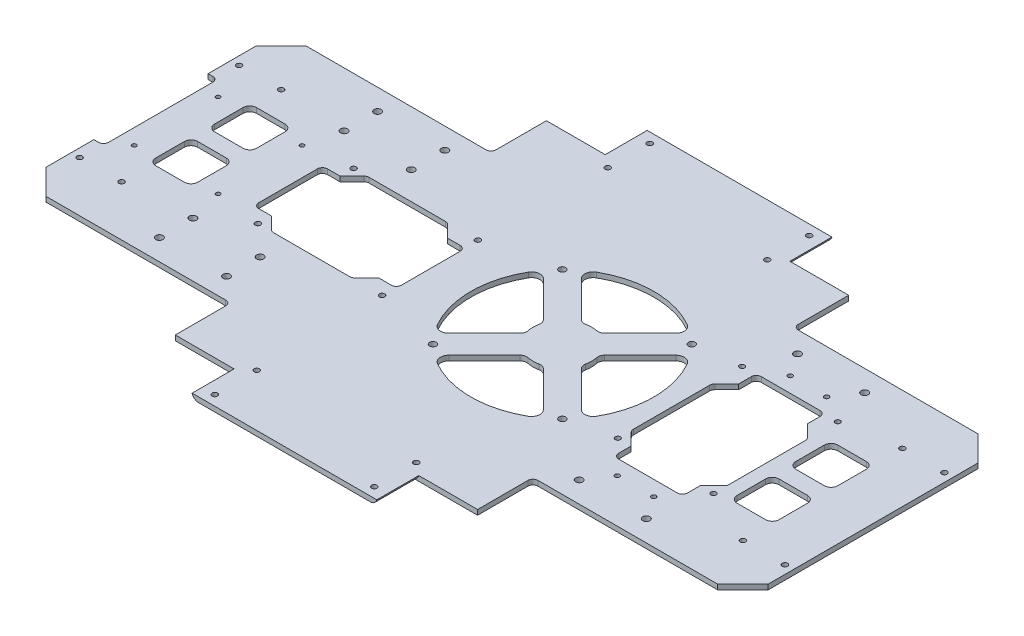
SolidWorks part; units mm, degrees
ref_plane "前视基准面" through (0, 0, 0) normal (0, 0, 1) x (1, 0, 0)
ref_plane "上视基准面" through (0, 0, 0) normal (0, 1, 0) x (1, 0, 0)
ref_plane "右视基准面" through (0, 0, 0) normal (1, 0, 0) x (0, 0, -1)
sketch "草图1" plane through (0, 0, 0) normal (0, 1, 0) x (1, 0, 0)
  line L0 (-82.9301, 135.4999) -> (-82.9301, 112.4999)
  line L1 (77.0699, 77.4999) -> (77.0699, -77.4999)
  line L2 (-47.9301, 77.4999) -> (77.0699, 77.4999)
  line L3 (-137.9301, 0) -> (-352.9301, 0) construction
  line L4 (-47.9301, -77.4999) -> (77.0699, -77.4999)
  line L5 (-137.9301, 112.4999) -> (-137.9301, -112.4999) construction
  line L6 (-137.9301, 0) -> (77.0699, 0) construction
  line L7 (-227.9301, -77.4999) -> (-352.9301, -77.4999)
  line L8 (-82.9301, 135.4999) -> (-192.9301, 135.4999)
  line L9 (-192.9301, 135.4999) -> (-192.9301, 112.4999)
  line L10 (-192.9301, -135.4999) -> (-82.9301, -135.4999)
  line L11 (-82.9301, -135.4999) -> (-82.9301, -112.4999)
  line L12 (-47.9301, 112.4999) -> (-47.9301, 77.4999)
  line L13 (-227.9301, 77.4999) -> (-352.9301, 77.4999)
  line L14 (-352.9301, 77.4999) -> (-352.9301, -77.4999)
  line L15 (-192.9301, -112.4999) -> (-192.9301, -135.4999)
  line L16 (-47.9301, -112.4999) -> (-82.9301, -112.4999)
  line L17 (-47.9301, 112.4999) -> (-82.9301, 112.4999)
  line L18 (-47.9301, -112.4999) -> (-47.9301, -77.4999)
  line L19 (-227.9301, -112.4999) -> (-227.9301, -77.4999)
  line L20 (-227.9301, -112.4999) -> (-192.9301, -112.4999)
  line L21 (-227.9301, 112.4999) -> (-192.9301, 112.4999)
  line L22 (-227.9301, 112.4999) -> (-227.9301, 77.4999)
  point P7 (77.0699, 0)
extrude "凸台-拉伸1" add sketch "草图1" along normal blind 3
fillet "圆角1" radius 3 8 edges at (-227.9301, 1.5, -77.4999) (-192.9301, 1.5, -112.4999) (-227.9301, 1.5, 77.4999) (-192.9301, 1.5, 112.4999) (-82.9301, 1.5, 112.4999) (-47.9301, 1.5, 77.4999) (-47.9301, 1.5, -77.4999) (-82.9301, 1.5, -112.4999)
sketch "草图2" plane through (0, 3, 0) normal (0, 1, 0) x (1, 0, 0)
  line L0 (77.0699, 47.5) -> (72.0699, 47.5) construction
  line L1 (72.0699, 47.5) -> (47.0699, 47.5) construction
  line L2 (47.0699, 47.5) -> (47.0699, -47.5) construction
  line L3 (47.0699, -47.5) -> (72.0699, -47.5) construction
  line L4 (72.0699, -47.5) -> (72.0699, 47.5) construction
  line L5 (72.0699, -47.5) -> (77.0699, -47.5) construction
  line L6 (77.0699, 0) -> (-352.9301, 0) construction
  line L7 (77.0699, -77.4999) -> (77.0699, 77.4999) construction
  line L8 (-352.9301, 77.4999) -> (-352.9301, -77.4999) construction
  line L9 (77.0699, 47.5) -> (77.0699, -47.5) construction
  line L10 (-137.9301, 135.4999) -> (-137.9301, -135.4999) construction
  line L11 (-82.9301, 135.4999) -> (-192.9301, 135.4999) construction
  line L12 (-192.9301, -135.4999) -> (-82.9301, -135.4999) construction
  line L13 (-90.4301, 104.4999) -> (-90.4301, 129.4999) construction
  line L14 (-90.4301, 129.4999) -> (-90.4301, 135.4999) construction
  line L15 (-185.4301, 135.4999) -> (-185.4301, 129.4999) construction
  line L16 (-185.4301, 104.4999) -> (-90.4301, 104.4999) construction
  line L17 (-185.4301, 135.4999) -> (-90.4301, 135.4999) construction
  line L18 (-185.4301, 129.4999) -> (-185.4301, 104.4999) construction
  line L19 (-90.4301, 129.4999) -> (-185.4301, 129.4999) construction
  line L20 (-90.4301, -129.4999) -> (-185.4301, -129.4999) construction
  line L21 (-185.4301, -129.4999) -> (-185.4301, -104.4999) construction
  line L22 (-185.4301, -135.4999) -> (-90.4301, -135.4999) construction
  line L23 (-185.4301, -104.4999) -> (-90.4301, -104.4999) construction
  line L24 (-185.4301, -135.4999) -> (-185.4301, -129.4999) construction
  line L25 (-90.4301, -129.4999) -> (-90.4301, -135.4999) construction
  line L26 (-90.4301, -104.4999) -> (-90.4301, -129.4999) construction
  line L27 (-352.9301, 47.5) -> (-352.9301, -47.5) construction
  line L28 (-347.9301, -47.5) -> (-352.9301, -47.5) construction
  line L29 (-347.9301, -47.5) -> (-347.9301, 47.5) construction
  line L30 (-322.9301, -47.5) -> (-347.9301, -47.5) construction
  line L31 (-322.9301, 47.5) -> (-322.9301, -47.5) construction
  line L32 (-347.9301, 47.5) -> (-322.9301, 47.5) construction
  line L33 (-352.9301, 47.5) -> (-347.9301, 47.5) construction
  circle A0 centre (47.0699, 47.5) radius 1.6
  circle A1 centre (72.0699, 47.5) radius 1.6
  circle A2 centre (47.0699, -47.5) radius 1.6
  circle A3 centre (72.0699, -47.5) radius 1.6
  circle A4 centre (-185.4301, 104.4999) radius 1.6
  circle A5 centre (-90.4301, 129.4999) radius 1.6
  circle A6 centre (-90.4301, 104.4999) radius 1.6
  circle A7 centre (-185.4301, 129.4999) radius 1.6
  circle A8 centre (-185.4301, -129.4999) radius 1.6
  circle A9 centre (-90.4301, -104.4999) radius 1.6
  circle A10 centre (-90.4301, -129.4999) radius 1.6
  circle A11 centre (-185.4301, -104.4999) radius 1.6
  circle A12 centre (-347.9301, -47.5) radius 1.6
  circle A13 centre (-322.9301, -47.5) radius 1.6
  circle A14 centre (-347.9301, 47.5) radius 1.6
  circle A15 centre (-322.9301, 47.5) radius 1.6
extrude "切除-拉伸1" cut sketch "草图2" against normal blind 47
sketch "草图3" plane through (0, 3, 0) normal (0, 1, 0) x (1, 0, 0)
  line L0 (-137.9301, 135.4999) -> (-137.9301, -135.4999) construction
  line L1 (-82.9301, 135.4999) -> (-192.9301, 135.4999) construction
  line L2 (-192.9301, -135.4999) -> (-82.9301, -135.4999) construction
  line L3 (-137.9301, 0) -> (-262.9301, 0) construction
  line L4 (-137.9301, 0) -> (-12.9301, 0) construction
  line L5 (-262.9301, 0) -> (-262.9301, 55) construction
  line L6 (-12.9301, -34) -> (-12.9301, 34) construction
  line L7 (-12.9301, 0) -> (-12.9301, 62) construction
  line L8 (-12.9301, 0) -> (-12.9301, -62) construction
  line L9 (-282.9301, -45) -> (-242.9301, -65) construction
  line L10 (-282.9301, 65) -> (-242.9301, 65) construction
  line L11 (-282.9301, 65) -> (-282.9301, 45) construction
  line L12 (-282.9301, 45) -> (-242.9301, 45) construction
  line L13 (-242.9301, 65) -> (-242.9301, 45) construction
  line L14 (-282.9301, 65) -> (-242.9301, 45) construction
  line L15 (-282.9301, 45) -> (-242.9301, 65) construction
  line L16 (-282.9301, -65) -> (-242.9301, -45) construction
  line L17 (-242.9301, -65) -> (-242.9301, -45) construction
  line L18 (-282.9301, -45) -> (-242.9301, -45) construction
  line L19 (-282.9301, -65) -> (-282.9301, -45) construction
  line L20 (-282.9301, -65) -> (-242.9301, -65) construction
  line L21 (7.0699, -65) -> (-32.9301, -65) construction
  line L22 (7.0699, -65) -> (7.0699, -45) construction
  line L23 (7.0699, -45) -> (-32.9301, -45) construction
  line L24 (-32.9301, -65) -> (-32.9301, -45) construction
  line L25 (7.0699, -65) -> (-32.9301, -45) construction
  line L26 (7.0699, 45) -> (-32.9301, 65) construction
  line L27 (7.0699, 65) -> (-32.9301, 45) construction
  line L28 (-32.9301, 65) -> (-32.9301, 45) construction
  line L29 (7.0699, 45) -> (-32.9301, 45) construction
  line L30 (7.0699, 65) -> (7.0699, 45) construction
  line L31 (7.0699, 65) -> (-32.9301, 65) construction
  line L32 (7.0699, -45) -> (-32.9301, -65) construction
  line L33 (-12.9301, 0) -> (-12.9301, -62) construction
  line L34 (-12.9301, 0) -> (-12.9301, 55) construction
  line L35 (-337.9301, 25) -> (-337.9301, -25) construction
  line L36 (-23.767, 51.5) -> (-12.9301, 34) construction
  line L37 (-352.9301, 77.4999) -> (-352.9301, -77.4999) construction
  line L38 (-23.767, 51.5) -> (-2.0931, 51.5) construction
  line L39 (-12.9301, 34) -> (-2.0931, 51.5) construction
  line L40 (-12.9301, -34) -> (-23.767, -51.5) construction
  line L41 (-23.767, -51.5) -> (-2.0931, -51.5) construction
  line L42 (-2.0931, -51.5) -> (-12.9301, -34) construction
  line L43 (-30.1258, 30) -> (4.2656, 30) construction
  line L44 (-30.1258, 35) -> (4.2656, 35)
  line L45 (-30.1258, 25) -> (-12.9301, 25)
  line L46 (-30.1258, 12.5) -> (4.2656, 12.5) construction
  line L47 (-30.1258, 17.5) -> (4.2656, 17.5)
  line L48 (-30.1258, 7.5) -> (4.2656, 7.5)
  line L49 (-30.1258, -30) -> (4.2656, -30) construction
  line L50 (-30.1258, -35) -> (4.2656, -35)
  line L51 (-30.1258, -25) -> (4.2656, -25)
  line L52 (-30.1258, -12.5) -> (4.2656, -12.5) construction
  line L53 (-30.1258, -17.5) -> (4.2656, -17.5)
  line L54 (-30.1258, -7.5) -> (4.2656, -7.5)
  line L55 (-8.9301, 25) -> (4.2656, 25)
  line L57 (-12.9301, 25) -> (-8.9301, 25)
  line L60 (-16.9301, -35) -> (-8.9301, 35) construction
  line L61 (-16.9301, 35) -> (-8.9301, -35) construction
  circle A0 centre (-282.9301, 65) radius 2.1
  circle A1 centre (-282.9301, 45) radius 2.1
  circle A2 centre (-242.9301, 65) radius 2.1
  circle A3 centre (-242.9301, 45) radius 2.1
  circle A4 centre (-242.9301, -45) radius 2.1
  circle A5 centre (-242.9301, -65) radius 2.1
  circle A6 centre (-282.9301, -45) radius 2.1
  circle A7 centre (-282.9301, -65) radius 2.1
  circle A8 centre (7.0699, -65) radius 2.1
  circle A9 centre (7.0699, -45) radius 2.1
  circle A10 centre (-32.9301, -65) radius 2.1
  circle A11 centre (-32.9301, -45) radius 2.1
  circle A12 centre (-32.9301, 45) radius 2.1
  circle A13 centre (-32.9301, 65) radius 2.1
  circle A14 centre (7.0699, 45) radius 2.1
  circle A15 centre (7.0699, 65) radius 2.1
  circle A16 centre (-23.767, -51.5) radius 1.4
  circle A17 centre (-2.0931, -51.5) radius 1.4
  arc A18 (-30.1258, 35) -> (-30.1258, 25) centre (-30.1258, 30) ccw
  circle A19 centre (-23.767, 51.5) radius 1.4
  arc A20 (4.2656, 25) -> (4.2656, 35) centre (4.2656, 30) ccw
  circle A21 centre (-2.0931, 51.5) radius 1.4
  circle A22 centre (-337.9301, 25) radius 1.25
  circle A23 centre (-287.9301, 25) radius 1.25
  circle A24 centre (-287.9301, -25) radius 1.25
  circle A25 centre (-337.9301, -25) radius 1.25
  arc A26 (-30.1258, 17.5) -> (-30.1258, 7.5) centre (-30.1258, 12.5) ccw
  arc A27 (4.2656, 7.5) -> (4.2656, 17.5) centre (4.2656, 12.5) ccw
  arc A28 (-30.1258, -35) -> (-30.1258, -25) centre (-30.1258, -30) cw
  arc A29 (4.2656, -25) -> (4.2656, -35) centre (4.2656, -30) cw
  arc A30 (-30.1258, -17.5) -> (-30.1258, -7.5) centre (-30.1258, -12.5) cw
  arc A31 (4.2656, -7.5) -> (4.2656, -17.5) centre (4.2656, -12.5) cw
  point P66 (-352.9301, 0)
  point P68 (-12.9301, 30)
  point P76 (-12.9301, 12.5)
  point P83 (-12.9301, -30)
  point P90 (-12.9301, -12.5)
  dimension "D9" = 15
  dimension "D11" = 5
  dimension "D1" = 125
  dimension "D2" = 50
  dimension "D3" = 55
  dimension "D4" = 50
  dimension "D5" = 50
  dimension "D6" = 50
  dimension "D7" = 40
  dimension "D8" = 20
  dimension "D10" = 0
  dimension "D12" = 30
  dimension "D13" = 7.5
  dimension "D14" = 34.3914
extrude "切除-拉伸2" cut sketch "草图3" against normal blind 47
chamfer "倒角1" distance 15 angle 45 4 edges at (77.0699, 1.5, -77.4999) (77.0699, 1.5, 77.4999) (-352.9301, 1.5, 77.4999) (-352.9301, 1.5, -77.4999)
sketch "草图5" plane through (0, 3, 0) normal (0, 1, 0) x (1, 0, 0)
  line L0 (-68.5001, 28.1163) -> (-89.6587, 6.9576)
  line L1 (-89.6587, -6.9576) -> (-68.5001, -28.1163)
  line L2 (-79.8138, -39.43) -> (-100.9725, -18.2713)
  line L3 (-114.8877, -18.2713) -> (-136.0464, -39.43)
  line L4 (-147.3601, -28.1163) -> (-126.2014, -6.9576)
  line L5 (-126.2014, 6.9576) -> (-147.3601, 28.1163)
  line L6 (-136.0464, 39.43) -> (-114.8877, 18.2713)
  line L7 (-100.9725, 18.2713) -> (-79.8138, 39.43)
  line L8 (-102.3298, -7.7031) -> (-102.3298, 7.7679)
  line L9 (-104.3298, -2.9676) -> (-104.3298, -7.7031)
  line L10 (-104.3298, 7.7679) -> (-104.3298, 3.0324)
  line L11 (-116.9301, -0.9676) -> (-106.3298, -0.9676)
  line L12 (-106.3298, 1.0324) -> (-116.9301, 1.0324)
  line L13 (-352.9301, 0) -> (77.0699, 0) construction
  line L14 (-352.9301, 62.4999) -> (-352.9301, -62.4999) construction
  line L15 (77.0699, -62.4999) -> (77.0699, 62.4999) construction
  line L16 (-137.9301, -135.4999) -> (-137.9301, -67.6391) construction
  line L17 (-192.9301, -135.4999) -> (-82.9301, -135.4999) construction
  line L18 (-137.9301, -67.6391) -> (-107.9301, -67.6391) construction
  line L19 (-107.9301, -67.6391) -> (-107.9301, 0) construction
  circle A0 centre (-69.3928, 38.5373) radius 1.55
  circle A1 centre (-69.3928, -38.5373) radius 1.55
  circle A2 centre (-146.4674, -38.5373) radius 1.55
  circle A3 centre (-146.4674, 38.5373) radius 1.55
  arc A4 (-60.6246, -27.0637) -> (-60.6246, 27.0637) centre (-107.9301, 0) ccw
  arc A5 (-60.6246, 27.0637) -> (-68.5001, 28.1163) centre (-64.9645, 24.5808) ccw
  arc A6 (-89.6587, 6.9576) -> (-90.7559, 3.361) centre (-86.8303, 4.1292) ccw
  arc A7 (-90.7559, -3.361) -> (-90.7559, 3.361) centre (-107.9301, 0) ccw
  arc A8 (-90.7559, -3.361) -> (-89.6587, -6.9576) centre (-86.8303, -4.1292) ccw
  arc A9 (-68.5001, -28.1163) -> (-60.6246, -27.0637) centre (-64.9645, -24.5808) ccw
  arc A10 (-80.8664, -47.3055) -> (-79.8138, -39.43) centre (-83.3493, -42.9655) ccw
  arc A11 (-134.9937, -47.3055) -> (-80.8664, -47.3055) centre (-107.9301, 0) ccw
  arc A12 (-100.9725, -18.2713) -> (-104.5691, -17.1742) centre (-103.8009, -21.0998) ccw
  arc A13 (-111.291, -17.1742) -> (-104.5691, -17.1742) centre (-107.9301, 0) ccw
  arc A14 (-111.291, -17.1742) -> (-114.8877, -18.2713) centre (-112.0593, -21.0998) ccw
  arc A15 (-136.0464, -39.43) -> (-134.9937, -47.3055) centre (-132.5108, -42.9655) ccw
  arc A16 (-126.2014, -6.9576) -> (-125.1043, -3.361) centre (-129.0298, -4.1292) ccw
  arc A17 (-125.1043, 3.361) -> (-125.1043, -3.361) centre (-107.9301, 0) ccw
  arc A18 (-125.1043, 3.361) -> (-126.2014, 6.9576) centre (-129.0298, 4.1292) ccw
  arc A19 (-147.3601, 28.1163) -> (-155.2356, 27.0637) centre (-150.8956, 24.5808) ccw
  arc A20 (-155.2356, 27.0637) -> (-155.2356, -27.0637) centre (-107.9301, 0) ccw
  arc A21 (-155.2356, -27.0637) -> (-147.3601, -28.1163) centre (-150.8956, -24.5808) ccw
  arc A22 (-104.5691, 17.1742) -> (-111.291, 17.1742) centre (-107.9301, 0) ccw
  arc A23 (-114.8877, 18.2713) -> (-111.291, 17.1742) centre (-112.0593, 21.0998) ccw
  arc A24 (-104.5691, 17.1742) -> (-100.9725, 18.2713) centre (-103.8009, 21.0998) ccw
  arc A25 (-79.8138, 39.43) -> (-80.8664, 47.3055) centre (-83.3493, 42.9655) ccw
  arc A26 (-80.8664, 47.3055) -> (-134.9937, 47.3055) centre (-107.9301, 0) ccw
  arc A27 (-134.9937, 47.3055) -> (-136.0464, 39.43) centre (-132.5108, 42.9655) ccw
  arc A28 (-102.3298, 7.7679) -> (-104.3298, 7.7679) centre (-103.3298, 7.7679) ccw
  arc A29 (-104.3298, -7.7031) -> (-102.3298, -7.7031) centre (-103.3298, -7.7031) ccw
  arc A30 (-106.3298, 1.0324) -> (-104.3298, 3.0324) centre (-106.3298, 3.0324) ccw
  arc A31 (-104.3298, -2.9676) -> (-106.3298, -0.9676) centre (-106.3298, -2.9676) ccw
  arc A32 (-116.9301, 1.0324) -> (-116.9301, -0.9676) centre (-116.9301, 0.0324) ccw
extrude "切除-拉伸3" cut sketch "草图5" against normal blind 47
sketch "草图6" plane through (0, 3, 0) normal (0, 1, 0) x (1, 0, 0)
  line L0 (-260.7825, 28.5) -> (-186.7825, 28.5) construction
  line L1 (-260.7825, 28.5) -> (-260.7825, -28.5) construction
  line L2 (-260.7825, -28.5) -> (-186.7825, -28.5) construction
  line L3 (-186.7825, 28.5) -> (-186.7825, -28.5) construction
  line L4 (-352.9301, 0) -> (77.0699, 0) construction
  line L5 (-352.9301, 62.4999) -> (-352.9301, -62.4999) construction
  line L6 (77.0699, -62.4999) -> (77.0699, 62.4999) construction
  line L7 (-270.2825, -20.5) -> (-260.7825, -20.5)
  line L8 (-186.2825, -19.5) -> (-186.2825, 19.5)
  line L9 (-187.2825, 20.5) -> (-196.7825, 20.5)
  line L10 (-271.2825, 19.5) -> (-271.2825, -19.5)
  line L11 (-251.2825, -28.5) -> (-251.2825, -24.9) construction
  line L12 (-251.2825, -24.9) -> (-213.2825, -24.9) construction
  line L13 (-213.2825, -24.9) -> (-213.2825, -23.5) construction
  line L14 (-213.2825, -23.5) -> (-193.2825, -23.5) construction
  line L15 (-190.2825, -26.5) -> (-190.2825, -28.5) construction
  line L16 (-183.2825, -28.5) -> (-183.2825, 28.5) construction
  line L17 (-190.2825, 28.5) -> (-190.2825, 26.5) construction
  line L18 (-193.2825, 23.5) -> (-213.2825, 23.5) construction
  line L19 (-213.2825, 23.5) -> (-213.2825, 24.9) construction
  line L20 (-213.2825, 24.9) -> (-251.2825, 24.9) construction
  line L21 (-251.2825, 24.9) -> (-251.2825, 28.5) construction
  line L22 (-251.2825, 28.5) -> (-253.9086, 28.5) construction
  line L23 (-264.2825, 28.5) -> (-264.2825, 27.5) construction
  line L24 (-268.2825, 23.5) -> (-274.2825, 23.5) construction
  line L25 (-274.2825, 23.5) -> (-274.2825, -23.5) construction
  line L26 (-274.2825, -23.5) -> (-268.2825, -23.5) construction
  line L27 (-264.2825, -27.5) -> (-264.2825, -28.5) construction
  line L28 (-253.9086, -28.5) -> (-251.2825, -28.5) construction
  line L29 (-270.2825, 20.5) -> (-271.2825, 20.5)
  line L30 (-271.2825, 20.5) -> (-271.2825, 19.5)
  line L31 (-271.2825, -19.5) -> (-271.2825, -20.5)
  line L32 (-271.2825, -20.5) -> (-270.2825, -20.5)
  line L33 (-187.2825, -20.5) -> (-186.2825, -20.5)
  line L34 (-186.2825, -20.5) -> (-186.2825, -19.5)
  line L35 (-187.2825, 20.5) -> (-186.2825, 20.5)
  line L36 (-186.2825, 20.5) -> (-186.2825, 19.5)
  line L37 (-162.4301, 0) -> (-183.2825, 0) construction
  line L38 (-183.2825, 0) -> (-183.2825, 23.5) construction
  line L39 (-228.7825, 20.5) -> (-228.7825, 28.5) construction
  line L40 (-252.7825, 28.5) -> (-204.7825, 28.5)
  line L41 (-204.7825, 28.5) -> (-196.7825, 20.5)
  line L42 (-252.7825, 28.5) -> (-260.7825, 20.5)
  line L43 (-260.7825, 20.5) -> (-270.2825, 20.5)
  line L44 (-252.7825, -28.5) -> (-260.7825, -20.5)
  line L45 (-252.7825, -28.5) -> (-204.7825, -28.5)
  line L46 (-204.7825, -28.5) -> (-196.7825, -20.5)
  line L47 (-196.7825, -20.5) -> (-187.2825, -20.5)
  circle A0 centre (-260.7825, 28.5) radius 1.6
  circle A1 centre (-186.7825, 28.5) radius 1.6
  circle A2 centre (-260.7825, -28.5) radius 1.6
  circle A3 centre (-186.7825, -28.5) radius 1.6
  circle A4 centre (-186.7825, -28.5) radius 1.5 construction
  arc A5 (-190.2825, -26.5) -> (-193.2825, -23.5) centre (-193.2825, -26.5) ccw construction
  arc A6 (-190.2825, -28.5) -> (-183.2825, -28.5) centre (-186.7825, -28.5) ccw construction
  arc A7 (-183.2825, 28.5) -> (-190.2825, 28.5) centre (-186.7825, 28.5) ccw construction
  arc A8 (-193.2825, 23.5) -> (-190.2825, 26.5) centre (-193.2825, 26.5) ccw construction
  arc A9 (-257.9521, 30.5588) -> (-253.9086, 28.5) centre (-253.9086, 33.5) ccw construction
  arc A10 (-257.9521, 30.5588) -> (-264.2825, 28.5) centre (-260.7825, 28.5) ccw construction
  arc A11 (-268.2825, 23.5) -> (-264.2825, 27.5) centre (-268.2825, 27.5) ccw construction
  arc A12 (-264.2825, -27.5) -> (-268.2825, -23.5) centre (-268.2825, -27.5) ccw construction
  arc A13 (-264.2825, -28.5) -> (-257.9521, -30.5588) centre (-260.7825, -28.5) ccw construction
  arc A14 (-253.9086, -28.5) -> (-257.9521, -30.5588) centre (-253.9086, -33.5) ccw construction
  arc A15 (-155.2356, 27.0637) -> (-155.2356, -27.0637) centre (-107.9301, 0) ccw construction
  dimension "D1" = 3.2
  dimension "D2" = 3.2
  dimension "D3" = 3.2
  dimension "D4" = 3.2
extrude "切除-拉伸4" cut sketch "草图6" against normal blind 47
fillet "圆角2" radius 3 8 edges at (-204.7825, 1.5, 28.5) (-252.7825, 1.5, 28.5) (-271.2825, 1.5, 20.5) (-186.2825, 1.5, 20.5) (-186.2825, 1.5, -20.5) (-271.2825, 1.5, -20.5) (-204.7825, 1.5, -28.5) (-252.7825, 1.5, -28.5)
sketch "草图7" plane through (0, 3, 0) normal (0, 1, 0) x (1, 0, 0)
  line L1 (-337.9301, 25) -> (-337.9301, -25) construction
  line L2 (-337.9301, 0) -> (-347.1301, 0) construction
  line L3 (-347.1301, 0) -> (-347.1301, 34)
  line L4 (-347.1301, 0) -> (-347.1301, -34)
  line L5 (-347.1301, -34) -> (-352.9301, -34)
  line L6 (-352.9301, 62.4999) -> (-352.9301, -62.4999) construction
  line L7 (-347.1301, 34) -> (-352.9301, 34)
  line L8 (-352.9301, 34) -> (-352.9301, -34)
extrude "切除-拉伸5" cut sketch "草图7" against normal blind 47
fillet "圆角3" radius 3 2 edges at (-347.1301, 1.5, 34) (-347.1301, 1.5, -34)
sketch "草图8" plane through (0, 3, 0) normal (0, 1, 0) x (1, 0, 0)
  line L0 (-347.1301, 0) -> (-312.1301, 0)
  line L1 (77.0699, 0) -> (32.0699, 0) construction
  line L2 (-347.1301, -31) -> (-347.1301, 31) construction
  line L3 (-335.3508, 26.6608) -> (-288.9094, -26.6608) construction
  line L4 (-300.0305, -8.0391) -> (-300.0305, -25.0391)
  line L5 (-325.0305, -8.0391) -> (-325.0305, -25.0391)
  line L6 (-325.0305, 30.9609) -> (-300.0305, -29.0391) construction
  line L7 (-300.0305, 9.9609) -> (-300.0305, 26.9609)
  line L8 (77.0699, -62.4999) -> (77.0699, 62.4999) construction
  line L11 (47.0699, 9) -> (47.0699, 26)
  line L12 (26.0699, 5) -> (43.0699, 5)
  line L14 (26.0699, 30) -> (43.0699, 30)
  line L15 (22.0699, 9) -> (22.0699, 26)
  line L16 (22.0699, -9) -> (22.0699, -26)
  line L17 (26.0699, -30) -> (43.0699, -30)
  line L18 (26.0699, -5) -> (43.0699, -5)
  line L19 (47.0699, -9) -> (47.0699, -26)
  line L20 (-321.0305, 30.9609) -> (-304.0305, 30.9609)
  line L21 (-321.0305, 5.9609) -> (-304.0305, 5.9609)
  line L22 (-324.3388, -31.2402) -> (-300.0305, 30.9609) construction
  line L23 (-325.0305, 9.9609) -> (-325.0305, 26.9609)
  line L24 (-321.0305, -4.0391) -> (-304.0305, -4.0391)
  line L25 (-321.0305, -29.0391) -> (-304.0305, -29.0391)
  arc A0 (22.0699, -26) -> (26.0699, -30) centre (26.0699, -26) ccw
  arc A1 (43.0699, -30) -> (47.0699, -26) centre (43.0699, -26) ccw
  arc A2 (47.0699, -9) -> (43.0699, -5) centre (43.0699, -9) ccw
  arc A3 (26.0699, -5) -> (22.0699, -9) centre (26.0699, -9) ccw
  arc A4 (26.0699, 5) -> (22.0699, 9) centre (26.0699, 9) cw
  arc A5 (43.0699, 5) -> (47.0699, 9) centre (43.0699, 9) ccw
  arc A6 (47.0699, 26) -> (43.0699, 30) centre (43.0699, 26) ccw
  arc A7 (22.0699, 26) -> (26.0699, 30) centre (26.0699, 26) cw
  arc A8 (-300.0305, 26.9609) -> (-304.0305, 30.9609) centre (-304.0305, 26.9609) ccw
  arc A9 (-321.0305, -4.0391) -> (-325.0305, -8.0391) centre (-321.0305, -8.0391) ccw
  arc A10 (-325.0305, -25.0391) -> (-321.0305, -29.0391) centre (-321.0305, -25.0391) ccw
  arc A11 (-325.0305, 26.9609) -> (-321.0305, 30.9609) centre (-321.0305, 26.9609) cw
  arc A12 (-321.0305, 5.9609) -> (-325.0305, 9.9609) centre (-321.0305, 9.9609) cw
  arc A13 (-304.0305, -29.0391) -> (-300.0305, -25.0391) centre (-304.0305, -25.0391) ccw
  arc A14 (-304.0305, 5.9609) -> (-300.0305, 9.9609) centre (-304.0305, 9.9609) ccw
  arc A15 (-300.0305, -8.0391) -> (-304.0305, -4.0391) centre (-304.0305, -8.0391) ccw
  point P8 (-312.1301, 0)
  point P16 (34.9703, -0.9609)
  point P28 (22.0699, -30)
  point P34 (47.0699, -5)
  point P37 (22.0699, -5)
  point P40 (22.0699, 5)
  point P43 (47.0699, 5)
  dimension "D3" = 4
  dimension "D2" = 4
  dimension "D1" = 25
extrude "切除-拉伸6" cut sketch "草图8" against normal blind 47 contours L21 A14 L7 A8 L20 A11 L23 A12 | L4 A15 L24 A9 L5 A10 L25 A13 | A7 L15 A4 L12 A5 L11 A6 L14 | L18 A3 L16 A0 L17 A1 L19 A2
sketch "草图9" plane through (0, 3, 0) normal (0, 1, 0) x (1, 0, 0)
  line L0 (-137.9301, 135.4999) -> (-137.9301, 0) construction
  line L1 (-227.9301, 112.4999) -> (-198.5667, 112.4999)
  line L2 (-227.9301, 112.4999) -> (-227.9301, 110.4999)
  line L3 (-227.9301, 110.4999) -> (-192.9301, 110.4999)
  line L4 (-192.9301, 112.4999) -> (-192.9301, 110.4999)
  line L5 (-82.9301, 135.4999) -> (-192.9301, 135.4999) construction
  line L6 (-137.9301, 0) -> (77.0699, 0) construction
  line L7 (77.0699, -62.4999) -> (77.0699, 62.4999) construction
  line L8 (-192.9301, 112.4999) -> (-192.9301, 116.7715)
  line L9 (-192.9301, 116.7715) -> (-197.0435, 116.7715)
  line L10 (-197.0435, 116.7715) -> (-198.5667, 112.4999)
  line L11 (-78.8166, 116.7715) -> (-77.2934, 112.4999)
  line L12 (-82.9301, 116.7715) -> (-78.8166, 116.7715)
  line L13 (-82.9301, 112.4999) -> (-82.9301, 116.7715)
  line L14 (-82.9301, 112.4999) -> (-82.9301, 110.4999)
  line L15 (-47.9301, 110.4999) -> (-82.9301, 110.4999)
  line L16 (-47.9301, 112.4999) -> (-47.9301, 110.4999)
  line L17 (-47.9301, 112.4999) -> (-77.2934, 112.4999)
  line L18 (-47.9301, -112.4999) -> (-77.2934, -112.4999)
  line L19 (-47.9301, -112.4999) -> (-47.9301, -110.4999)
  line L20 (-47.9301, -110.4999) -> (-82.9301, -110.4999)
  line L21 (-82.9301, -112.4999) -> (-82.9301, -110.4999)
  line L22 (-82.9301, -112.4999) -> (-82.9301, -116.7715)
  line L23 (-82.9301, -116.7715) -> (-78.8166, -116.7715)
  line L24 (-78.8166, -116.7715) -> (-77.2934, -112.4999)
  line L25 (-197.0435, -116.7715) -> (-198.5667, -112.4999)
  line L26 (-192.9301, -116.7715) -> (-197.0435, -116.7715)
  line L27 (-192.9301, -112.4999) -> (-192.9301, -116.7715)
  line L28 (-192.9301, -112.4999) -> (-192.9301, -110.4999)
  line L29 (-227.9301, -110.4999) -> (-192.9301, -110.4999)
  line L30 (-227.9301, -112.4999) -> (-227.9301, -110.4999)
  line L31 (-227.9301, -112.4999) -> (-198.5667, -112.4999)
  dimension "D1" = 2
extrude "切除-拉伸7" cut sketch "草图9" against normal blind 10
sketch "草图12" plane through (0, 3, 0) normal (0, 1, 0) x (1, 0, 0)
  line L1 (-251.5398, 28.5) -> (-196.8231, 28.5)
  line L2 (-203.9038, 27.6213) -> (-214.5678, 38.2854)
  line L3 (-214.5678, 38.2854) -> (-189.8065, 13.524)
  line L4 (-189.8065, 13.524) -> (-196.7825, 20.5)
  line L5 (-196.7825, 20.5) -> (-178.29, 20.5)
  line L6 (-186.2825, 17.5) -> (-186.2825, -37.5464)
  line L7 (-186.2825, -37.5464) -> (-186.2825, 40.5353)
  line L8 (-196.7825, -20.5) -> (-175.2518, -20.5)
  line L9 (-178.29, 20.5) -> (-296.476, 20.5)
  line L10 (-260.7825, 20.5) -> (-237.3181, 43.9644)
  line L11 (-196.8231, 28.5) -> (-257.2832, 28.5)
  line L12 (-271.2825, -17.5) -> (-271.2825, 35.793)
  line L13 (-260.7825, 28.5) -> (-186.7825, 28.5)
  line L14 (-186.7825, 28.5) -> (-186.7825, -28.5)
  line L15 (-186.7825, -28.5) -> (-260.7825, -28.5)
  line L16 (-260.7825, -28.5) -> (-260.7825, 28.5)
  line L17 (-39.0535, 38.2854) -> (-39.0535, -37.5464)
  line L18 (-39.0535, -37.5464) -> (15.26, -37.5464)
  line L19 (15.26, -37.5464) -> (15.26, 38.2854)
  line L20 (15.26, 38.2854) -> (-39.0535, 38.2854)
  dimension "D1" = 85
  dimension "D2" = 41
  dimension "D3" = 8
  dimension "D4" = 10.5
  dimension "D5" = 0.5
extrude "凸台-拉伸5" add sketch "草图12" against normal blind 3 contours L19 L20 L17 L18
sketch "草图15" plane through (0, 3, 0) normal (0, 1, 0) x (1, 0, 0)
  line L0 (94.8136, 0) -> (-229.9674, 0)
  line L1 (-42.9301, 42.5) -> (-42.9301, -42.5)
  line L2 (-42.9301, -42.5) -> (14.0699, -42.5)
  line L3 (14.0699, -42.5) -> (14.0699, 42.5)
  line L4 (14.0699, 42.5) -> (-42.9301, 42.5)
  line L5 (-34.9301, 42.5) -> (-34.9301, -42.5)
  line L6 (-34.9301, -42.5) -> (6.0699, -42.5)
  line L7 (6.0699, -42.5) -> (6.0699, 42.5)
  line L8 (6.0699, 42.5) -> (6.0699, 32)
  line L9 (6.0699, 32) -> (14.0699, 24)
  line L10 (14.0699, 24) -> (14.0699, -24)
  line L11 (14.0699, -24) -> (6.0699, -32)
  line L12 (-34.9301, 32) -> (-42.9301, 24)
  line L13 (-42.9301, 24) -> (-42.9301, -24)
  line L14 (-42.9301, -24) -> (-34.9301, -32)
  line L15 (-34.9301, 32) -> (6.0699, 32)
  line L16 (6.0699, -32) -> (-34.9301, -32)
  line L17 (22.0699, 9) -> (22.0699, 26) construction
  dimension "D1" = 85
  dimension "D2" = 42.5
  dimension "D3" = 41
  dimension "D4" = 8
  dimension "D5" = 8
  dimension "D6" = 8
  dimension "D7" = 10.5
  dimension "D8" = 10.5
  dimension "D9" = 45
  dimension "D10" = 45
  dimension "D11" = 45
  dimension "D12" = 45
extrude "凸台-拉伸6" add sketch "草图15" against normal blind 16.5 separate body contours L5 L15 L7 L4 | L15 L5 L0 L7 | L5 L12 L1 L0 | L1 L14 L5 L0 | L16 L7 L0 L5 | L7 L16 L5 L2 | L11 L3 L0 L7 | L9 L7 L0 L3
combine bodies "组合2" operation type subtract main body 120 bodies to subtract 121
fillet "圆角5" radius 3 8 edges at (-42.9301, 1.5, 24) (-42.9301, 1.5, -24) (-34.9301, 1.5, -42.5) (6.0699, 1.5, -42.5) (14.0699, 1.5, -24) (14.0699, 1.5, 24) (6.0699, 1.5, 42.5) (-34.9301, 1.5, 42.5)
sketch "草图16" plane through (0, 3, 0) normal (0, 1, 0) x (1, 0, 0)
  line L1 (-35.878, 47.8829) -> (10.5854, 47.8829)
  line L2 (-35.878, 47.8829) -> (-35.878, 42.7034)
  line L3 (-35.878, 42.7034) -> (10.5854, 42.7034)
  line L4 (10.5854, 47.8829) -> (10.5854, 42.7034)
  line L5 (-37.2372, -48.0584) -> (11.2328, -48.0584)
  line L6 (-37.2372, -48.0584) -> (-37.2372, -42.6499)
  line L7 (-37.2372, -42.6499) -> (11.2328, -42.6499)
  line L8 (11.2328, -48.0584) -> (11.2328, -42.6499)
extrude "凸台-拉伸7" add sketch "草图16" against normal blind 3 contours L2 L1 L4 L3 | L6 L5 L8 L7
sketch "草图17" plane through (0, 3, 0) normal (0, 1, 0) x (1, 0, 0)
  line L0 (-45.1726, 42) -> (21.2748, 42)
  line L1 (3.0699, 42.5) -> (-31.9301, 42.5) construction
  line L2 (-42.9301, -22.7574) -> (-42.9301, 46.7455)
  line L3 (-42.9301, 46.7455) -> (-42.9301, -41.9985)
  line L4 (14.0699, -22.7574) -> (14.0699, 48.9856)
  line L5 (14.0699, 48.9856) -> (14.0699, -48.2019)
  line L6 (-34.9301, -32) -> (19.0836, -32)
  line L7 (19.0836, -32) -> (-50.016, -32)
  circle A0 centre (-42.9301, 42) radius 1.5
  circle A1 centre (14.0699, 42) radius 1.5
  circle A2 centre (14.0699, -32) radius 1.5
  circle A3 centre (-42.9301, -32) radius 1.5
  dimension "D2" = 3
  dimension "D3" = 3
  dimension "D4" = 3
  dimension "D5" = 3
  dimension "D1" = 0.5
extrude "凸台-拉伸8" add sketch "草图17" against normal blind 13 separate body contours L3 A3 L7 | L3 A3 L7 | L7 A3 L3 | L7 A3 L3 | L6 A2 L5 | L5 A2 L7 | L7 A2 L5 | L5 A2 L6 | L0 A1 L4 | L4 A1 L0 | L0 A1 L5 | L5 A1 L0 | A0
combine bodies "组合3" operation type subtract main body 123 bodies to subtract 125 124 127 126
fillet "圆角6" radius 4 4 edges at (-192.9301, 0, -122.9999) (-82.9301, 0, -122.9999) (-192.9301, 0, 122.9999) (-82.9301, 0, 122.9999)
sketch "草图18" plane through (0, 3, 0) normal (0, 1, 0) x (1, 0, 0)
  line L0 (-260.7825, 28.5) -> (-186.7825, 28.5)
  line L1 (-186.7825, 28.5) -> (-186.7825, -28.5)
  line L2 (-186.7825, -28.5) -> (-260.7825, -28.5)
  line L3 (-260.7825, -28.5) -> (-260.7825, 28.5)
  line L4 (-271.2825, 17.5) -> (-271.2825, -22.4528)
  line L5 (-271.2825, -22.4528) -> (-271.2825, 32.5301)
  line L6 (-271.2825, 32.5301) -> (-271.2825, -34.5796)
  line L7 (-260.7825, 28.5) -> (-271.2825, 28.5)
  line L8 (-260.7825, -28.5) -> (-271.2825, -28.5)
  line L9 (-260.7825, 20.5) -> (-247.7298, 33.5527)
  line L10 (-196.7825, 20.5) -> (-209.8351, 33.5527)
  line L11 (-260.7825, 20.5) -> (-276.73, 20.5)
  line L12 (-276.73, 20.5) -> (-183.2474, 20.5)
  line L13 (-186.2825, -17.5) -> (-186.2825, 33.5527)
  line L14 (-186.2825, -17.5) -> (-186.2825, 17.5) construction
  line L15 (-186.2825, 33.5527) -> (-186.2825, -33.52)
  dimension "D1" = 74
  dimension "D2" = 57
  dimension "D3" = 0.5
  dimension "D4" = 10.5
  dimension "D5" = 8
  dimension "D6" = 10
sketch "草图19" plane through (0, 3, 0) normal (0, 1, 0) x (1, 0, 0)
  line L0 (-106.3298, 1.0324) -> (-116.9301, 1.0324) construction
  circle A0 centre (-110.0206, 1.0324) radius 13.1472
extrude "凸台-拉伸11" add sketch "草图19" against normal blind 3
sketch "草图20" plane through (0, 3, 0) normal (0, 1, 0) x (1, 0, 0)
  circle A0 centre (-69.3928, -38.5373) radius 2
  circle A1 centre (-146.4674, -38.5373) radius 2
  circle A2 centre (-146.4674, 38.5373) radius 2
  circle A3 centre (-69.3928, 38.5373) radius 2
  dimension "D1" = 4
  dimension "D2" = 4
  dimension "D3" = 4
  dimension "D4" = 4
extrude "切除-拉伸8" cut sketch "草图20" against normal blind 10
